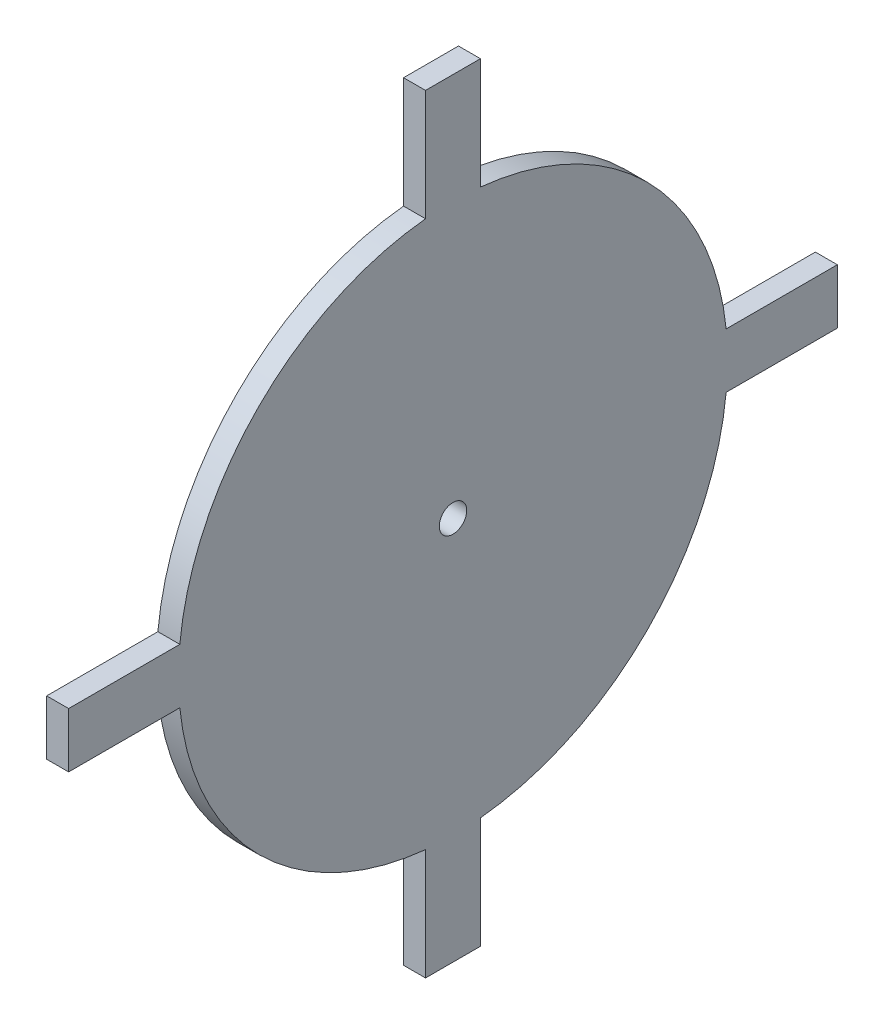
SolidWorks part; units mm, degrees
ref_plane "Front Plane" through (0, 0, 0) normal (0, 0, 1) x (1, 0, 0)
ref_plane "Top Plane" through (0, 0, 0) normal (0, 1, 0) x (1, 0, 0)
ref_plane "Right Plane" through (0, 0, 0) normal (1, 0, 0) x (0, 0, -1)
sketch "Sketch1" plane through (0, 0, 0) normal (1, 0, 0) x (0, 0, -1)
  line L1 (-6.35, 88.9) -> (6.35, 88.9)
  line L2 (-6.35, 88.9) -> (-6.35, -88.9)
  line L3 (-6.35, -88.9) -> (6.35, -88.9)
  line L4 (6.35, 88.9) -> (6.35, -88.9)
  line L5 (-6.35, 88.9) -> (6.35, -88.9) construction
  line L6 (-6.35, -88.9) -> (6.35, 88.9) construction
  line L7 (-88.9, -6.35) -> (88.9, -6.35)
  line L8 (-88.9, -6.35) -> (-88.9, 6.35)
  line L9 (-88.9, 6.35) -> (88.9, 6.35)
  line L10 (88.9, -6.35) -> (88.9, 6.35)
  line L11 (-88.9, -6.35) -> (88.9, 6.35) construction
  line L12 (-88.9, 6.35) -> (88.9, -6.35) construction
  circle A0 centre (0, 0) radius 63.5
  circle A1 centre (0, 0) radius 3.175
  dimension "D1" = 127
  dimension "D6" = 6.35
  dimension "D2" = 12.7
  dimension "D3" = 12.7
  dimension "D4" = 177.8
  dimension "D5" = 177.8
extrude "Boss-Extrude1" add sketch "Sketch1" along normal blind 5.08 contours L9 A0 L4 | A0 L4 L1 L2 | L4 A0 L2 L9 | L2 A0 L9 | A0 L9 L8 L7 | L9 A0 L7 L2 | L7 A0 L2 | L4 A0 L7 | L7 A0 L9 L4 | A0 L7 L10 L9 | L9 L2 L7 L4 | L2 A0 L4 L7 | A0 L2 L3 L4 region at (0, 76.1468, 0) region at (0, 34.8721, 0) region at (0, 29.7404, 29.7404) region at (0, 29.7404, -29.7404) region at (0, 6.1704, 0) region at (0, 0, 34.8721) region at (0, 0, 76.1468) region at (0, 0, -34.8721) region at (0, 0, -76.1468) region at (0, -34.8721, 0) region at (0, -29.7404, 29.7404) region at (0, -29.7404, -29.7404) region at (0, -76.1468, 0)
